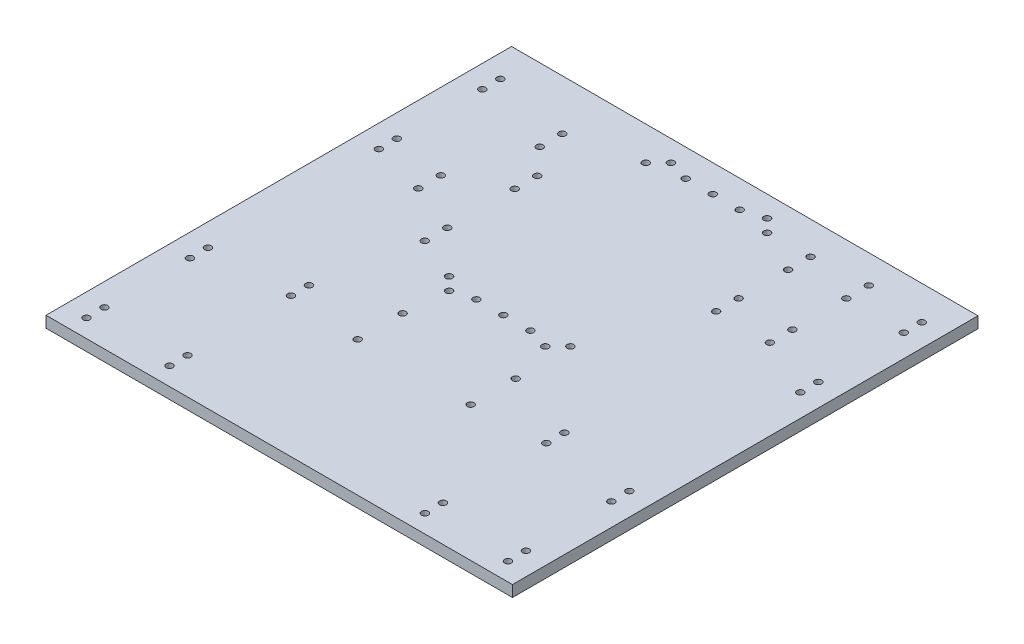
SolidWorks part; units mm, degrees
ref_plane "Front Plane" through (0, 0, 0) normal (0, 0, 1) x (1, 0, 0)
ref_plane "Top Plane" through (0, 0, 0) normal (0, 1, 0) x (1, 0, 0)
ref_plane "Right Plane" through (0, 0, 0) normal (1, 0, 0) x (0, 0, -1)
sketch "Sketch1" plane through (0, 0, 0) normal (0, 1, 0) x (1, 0, 0)
  line L1 (131.7003, -127) -> (-131.7003, -127)
  line L2 (131.7003, -127) -> (131.7003, 127)
  line L3 (131.7003, 127) -> (-131.7003, 127)
  line L4 (-131.7003, -127) -> (-131.7003, 127)
  line L5 (131.7003, -127) -> (-131.7003, 127) construction
  line L6 (131.7003, 127) -> (-131.7003, -127) construction
  point P0 (0, 0)
  dimension "D1" = 263.4005
  dimension "D2" = 254
extrude "Boss-Extrude1" add sketch "Sketch1" along normal blind 6.35
hole_wizard "#6 Clearance Hole1" positions "Sketch3" profile "Sketch4" hole size "#6" standard "ANSI Inch" end condition through all
sketch "Sketch3" plane through (0, 6.35, 0) normal (0, 1, 0) x (1, 0, 0)
  line L0 (131.7003, 127) -> (-131.7003, 127) construction
  line L1 (119.0003, 116.84) -> (119.0003, 106.68)
  line L3 (119.0003, 58.42) -> (119.0003, 48.26)
  line L5 (131.7003, -127) -> (131.7003, 127) construction
  point P0 (119.0003, 116.84)
  point P2 (119.0003, 106.68)
  point P4 (119.0003, 58.42)
  point P6 (119.0003, 48.26)
  dimension "D1" = 10.16
  dimension "D2" = 10.16
  dimension "D3" = 48.26
  dimension "D4" = 12.7
  dimension "D5" = 12.7
  dimension "D6" = 10.16
sketch "Sketch4" plane through (119.0003, 6.35, -116.84) normal (1, 0, 0) x (0, 0, 1)
  line L0 (0, 0) -> (0, 6.35)
  line L1 (0, 6.35) -> (1.8986, 6.35)
  line L2 (1.8986, 6.35) -> (1.8986, 0)
  line L5 (1.8986, 0) -> (0, 0)
  line L11 (0, -6.35) -> (0, 107.95) construction
  dimension "Thru Hole Dia." = 3.7973
  dimension "Thru Hole Depth" = 6.35
ref_plane "Plane1" through (0, 0, 0) normal (0, 0, -1) x (-1, 0, 0)
mirror "Mirror1" about plane through (0, 0, 0) normal (0, 0, -1) of "#6 Clearance Hole1"
hole_wizard "#6 Clearance Hole2" positions "Sketch5" profile "Sketch6" hole size "#6" standard "ANSI Inch" end condition through all
sketch "Sketch5" plane through (0, 6.35, 0) normal (0, 1, 0) x (1, 0, 0)
  line L0 (86.0793, 119.8956) -> (86.0793, 107.1956)
  line L2 (86.0793, 76.7156) -> (86.0793, 64.0156)
  line L4 (131.7003, -127) -> (131.7003, 127) construction
  line L5 (131.7003, 127) -> (-131.7003, 127) construction
  point P0 (86.0793, 119.8956)
  point P2 (86.0793, 107.1956)
  point P4 (86.0793, 76.7156)
  point P6 (86.0793, 64.0156)
  dimension "D1" = 45.6209
  dimension "D2" = 45.6209
  dimension "D3" = 12.7
  dimension "D4" = 12.7
  dimension "D5" = 7.1044
  dimension "D6" = 30.48
sketch "Sketch6" plane through (86.0793, 6.35, -119.8956) normal (1, 0, 0) x (0, 0, 1)
  line L0 (0, 0) -> (0, 6.35)
  line L1 (0, 6.35) -> (1.8986, 6.35)
  line L2 (1.8986, 6.35) -> (1.8986, 0)
  line L5 (1.8986, 0) -> (0, 0)
  line L11 (0, -6.35) -> (0, 107.95) construction
  dimension "Thru Hole Dia." = 3.7973
  dimension "Thru Hole Depth" = 6.35
hole_wizard "#6 Clearance Hole3" positions "Sketch7" profile "Sketch8" hole size "#6" standard "ANSI Inch" end condition through all
sketch "Sketch7" plane through (0, 6.35, 0) normal (0, 1, 0) x (1, 0, 0)
  line L0 (55.5993, 76.802) -> (55.5993, 64.102)
  line L3 (55.5993, 117.442) -> (55.5993, 104.742)
  circle A0 centre (86.0793, 107.1956) radius 1.8986 construction
  circle A1 centre (86.0793, 64.0156) radius 1.8986 construction
  circle A3 centre (86.0793, 119.8956) radius 1.8986 construction
  point P0 (55.5993, 117.442)
  point P2 (55.5993, 104.742)
  point P4 (55.5993, 76.802)
  point P6 (55.5993, 64.102)
  dimension "D6" = 27.94
  dimension "D1" = 12.7
  dimension "D2" = 12.7
  dimension "D3" = 30.48
  dimension "D4" = 30.48
  dimension "D5" = 2.4536
sketch "Sketch8" plane through (55.5993, 6.35, -117.442) normal (1, 0, 0) x (0, 0, 1)
  line L0 (0, 0) -> (0, 6.35)
  line L1 (0, 6.35) -> (1.8986, 6.35)
  line L2 (1.8986, 6.35) -> (1.8986, 0)
  line L5 (1.8986, 0) -> (0, 0)
  line L11 (0, -6.35) -> (0, 107.95) construction
  dimension "Thru Hole Dia." = 3.7973
  dimension "Thru Hole Depth" = 6.35
hole_wizard "#6 Clearance Hole4" positions "Sketch9" profile "Sketch10" hole size "#6" standard "ANSI Inch" end condition through all
sketch "Sketch9" plane through (0, 6.35, 0) normal (0, 1, 0) x (1, 0, 0)
  line L0 (72.1119, -38.1) -> (72.1119, -48.26)
  line L2 (72.1119, -106.68) -> (72.1119, -116.84)
  line L4 (131.7003, -127) -> (131.7003, 127) construction
  line L5 (-131.7003, -127) -> (131.7003, -127) construction
  point P0 (72.1119, -38.1)
  point P2 (72.1119, -48.26)
  point P4 (72.1119, -106.68)
  point P6 (72.1119, -116.84)
  dimension "D1" = 10.16
  dimension "D2" = 10.16
  dimension "D3" = 59.5884
  dimension "D4" = 59.5884
  dimension "D5" = 58.42
  dimension "D6" = 10.16
sketch "Sketch10" plane through (72.1119, 6.35, 38.1) normal (1, 0, 0) x (0, 0, 1)
  line L0 (0, 0) -> (0, 6.35)
  line L1 (0, 6.35) -> (1.8986, 6.35)
  line L2 (1.8986, 6.35) -> (1.8986, 0)
  line L5 (1.8986, 0) -> (0, 0)
  line L11 (0, -6.35) -> (0, 107.95) construction
  dimension "Thru Hole Dia." = 3.7973
  dimension "Thru Hole Depth" = 6.35
ref_plane "Plane2" through (0, 0, 0) normal (-1, 0, 0) x (0, 0, 1)
mirror "Mirror2" about plane through (0, 0, 0) normal (-1, 0, 0) of "#6 Clearance Hole4", "#6 Clearance Hole1", "Mirror1"
hole_wizard "#6 Clearance Hole5" positions "Sketch11" profile "Sketch12" hole size "#6" standard "ANSI Inch" end condition through all
sketch "Sketch11" plane through (0, 6.35, 0) normal (0, 1, 0) x (1, 0, 0)
  line L0 (-74.6519, 107.475) -> (-74.6519, 94.775)
  line L2 (-88.6219, 52.8626) -> (-88.6219, 40.1626)
  line L4 (131.7003, 127) -> (-131.7003, 127) construction
  line L5 (-131.7003, 127) -> (-131.7003, -127) construction
  point P0 (-74.6519, 107.475)
  point P2 (-74.6519, 94.775)
  point P4 (-88.6219, 52.8626)
  point P6 (-88.6219, 40.1626)
  dimension "D1" = 12.7
  dimension "D2" = 12.7
  dimension "D3" = 19.525
  dimension "D4" = 43.0784
  dimension "D5" = 57.0484
  dimension "D6" = 41.9125
sketch "Sketch12" plane through (-74.6519, 6.35, -107.475) normal (1, 0, 0) x (0, 0, 1)
  line L0 (0, 0) -> (0, 6.35)
  line L1 (0, 6.35) -> (1.8986, 6.35)
  line L2 (1.8986, 6.35) -> (1.8986, 0)
  line L5 (1.8986, 0) -> (0, 0)
  line L11 (0, -6.35) -> (0, 107.95) construction
  dimension "Thru Hole Dia." = 3.7973
  dimension "Thru Hole Depth" = 6.35
hole_wizard "#6 Clearance Hole6" positions "Sketch13" profile "Sketch14" hole size "#6" standard "ANSI Inch" end condition through all
sketch "Sketch13" plane through (0, 6.35, 0) normal (0, 1, 0) x (1, 0, 0)
  line L0 (-61.1569, 79.85) -> (-61.1569, 67.15)
  line L2 (-61.1569, 29.05) -> (-61.1569, 16.35)
  line L4 (-131.7003, 127) -> (-131.7003, -127) construction
  line L5 (131.7003, 127) -> (-131.7003, 127) construction
  point P0 (-61.1569, 79.85)
  point P2 (-61.1569, 67.15)
  point P4 (-61.1569, 29.05)
  point P6 (-61.1569, 16.35)
  dimension "D1" = 12.7
  dimension "D2" = 12.7
  dimension "D3" = 70.5434
  dimension "D4" = 70.5434
  dimension "D5" = 110.65
  dimension "D6" = 47.15
sketch "Sketch14" plane through (-61.1569, 6.35, -79.85) normal (1, 0, 0) x (0, 0, 1)
  line L0 (0, 0) -> (0, 6.35)
  line L1 (0, 6.35) -> (1.8986, 6.35)
  line L2 (1.8986, 6.35) -> (1.8986, 0)
  line L5 (1.8986, 0) -> (0, 0)
  line L11 (0, -6.35) -> (0, 107.95) construction
  dimension "Thru Hole Dia." = 3.7973
  dimension "Thru Hole Depth" = 6.35
hole_wizard "#6 Clearance Hole8" positions "Sketch15" profile "Sketch16" hole size "#6" standard "ANSI Inch" end condition through all
sketch "Sketch15" plane through (0, 6.35, 0) normal (0, 1, 0) x (1, 0, 0)
  line L2 (-36.9176, -1.2929) -> (-29.8056, -1.2929)
  line L3 (-36.9176, -1.2929) -> (-36.9176, 5.8191)
  line L4 (-36.9176, 5.8191) -> (-29.8056, 5.8191)
  line L5 (-29.8056, -1.2929) -> (-29.8056, 5.8191)
  line L6 (131.7003, 127) -> (-131.7003, 127) construction
  line L7 (-131.7003, 127) -> (-131.7003, -127) construction
  point P0 (-36.9176, 5.8191)
  point P6 (-29.8056, -1.2929)
  dimension "D1" = 94.7826
  dimension "D2" = 7.112
  dimension "D3" = 7.112
  dimension "D4" = 121.1809
sketch "Sketch16" plane through (-36.9176, 6.35, -5.8191) normal (1, 0, 0) x (0, 0, 1)
  line L0 (0, 0) -> (0, 6.35)
  line L1 (0, 6.35) -> (1.8986, 6.35)
  line L2 (1.8986, 6.35) -> (1.8986, 0)
  line L5 (1.8986, 0) -> (0, 0)
  line L11 (0, -6.35) -> (0, 107.95) construction
  dimension "Thru Hole Dia." = 3.7973
  dimension "Thru Hole Depth" = 6.35
hole_wizard "#6 Clearance Hole9" positions "Sketch17" profile "Sketch18" hole size "#6" standard "ANSI Inch" end condition through all
sketch "Sketch17" plane through (0, 6.35, 0) normal (0, 1, 0) x (1, 0, 0)
  line L1 (-36.9176, 116.8603) -> (-29.8056, 116.8603)
  line L2 (-36.9176, 116.8603) -> (-36.9176, 123.9723)
  line L3 (-36.9176, 123.9723) -> (-29.8056, 123.9723)
  line L4 (-29.8056, 116.8603) -> (-29.8056, 123.9723)
  circle A1 centre (-36.9176, 5.8191) radius 1.8987 construction
  circle A3 centre (-29.8056, -1.2929) radius 1.8986 construction
  point P2 (-29.8056, 123.9723)
  point P4 (-36.9176, 116.8603)
  dimension "D1" = 125.2652
  dimension "D2" = 7.112
  dimension "D3" = 7.112
  dimension "D4" = 0
sketch "Sketch18" plane through (-29.8056, 6.35, -123.9723) normal (1, 0, 0) x (0, 0, 1)
  line L0 (0, 0) -> (0, 6.35)
  line L1 (0, 6.35) -> (1.8986, 6.35)
  line L2 (1.8986, 6.35) -> (1.8986, 0)
  line L5 (1.8986, 0) -> (0, 0)
  line L11 (0, -6.35) -> (0, 107.95) construction
  dimension "Thru Hole Dia." = 3.7973
  dimension "Thru Hole Depth" = 6.35
hole_wizard "#6 Clearance Hole10" positions "Sketch19" profile "Sketch20" hole size "#6" standard "ANSI Inch" end condition through all
sketch "Sketch19" plane through (0, 6.35, 0) normal (0, 1, 0) x (1, 0, 0)
  line L0 (-17.8903, 120.4163) -> (12.5893, 120.4163)
  line L1 (12.5893, 120.4163) -> (-2.6505, 120.4163)
  line L3 (24.5046, 123.9723) -> (31.6166, 123.9723)
  line L4 (24.5046, 123.9723) -> (24.5046, 116.8603)
  line L5 (24.5046, 116.8603) -> (31.6166, 116.8603)
  line L6 (31.6166, 123.9723) -> (31.6166, 116.8603)
  line L9 (24.5046, -1.2929) -> (31.6166, -1.2929)
  line L10 (24.5046, -1.2929) -> (24.5046, 5.8191)
  line L11 (24.5046, 5.8191) -> (31.6166, 5.8191)
  line L12 (31.6166, -1.2929) -> (31.6166, 5.8191)
  circle A0 centre (-29.8056, -1.2929) radius 1.8986 construction
  circle A1 centre (-29.8056, 123.9723) radius 1.8987 construction
  point P0 (-17.8905, 2.2631)
  point P2 (-2.6505, 2.2631)
  point P4 (12.5895, 2.2631)
  point P10 (-17.8903, 120.4163)
  point P12 (-2.6505, 120.4952)
  point P14 (12.5893, 120.4163)
  point P32 (24.5046, 123.9723)
  point P34 (31.6166, 116.8603)
  point P36 (24.5046, -1.2929)
  point P38 (31.6166, 5.8191)
  dimension "D1" = 27.1551
  dimension "D4" = 3.556
  dimension "D5" = 3.556
  dimension "D2" = 15.24
  dimension "D3" = 15.24
  dimension "D6" = 3.556
  dimension "D7" = 15.24
  dimension "D8" = 15.24
  dimension "D9" = 27.1551
  dimension "D10" = 3.556
  dimension "D11" = 27.1551
  dimension "D12" = 7.112
  dimension "D13" = 7.112
  dimension "D14" = 3.556
  dimension "D15" = 7.112
  dimension "D16" = 7.112
  dimension "D17" = 3.556
  dimension "D18" = 11.9151
sketch "Sketch20" plane through (-17.8905, 6.35, -2.2631) normal (1, 0, 0) x (0, 0, 1)
  line L0 (0, 0) -> (0, 6.35)
  line L1 (0, 6.35) -> (1.8986, 6.35)
  line L2 (1.8986, 6.35) -> (1.8986, 0)
  line L5 (1.8986, 0) -> (0, 0)
  line L11 (0, -6.35) -> (0, 107.95) construction
  dimension "Thru Hole Dia." = 3.7973
  dimension "Thru Hole Depth" = 6.35
hole_wizard "#6 Clearance Hole7" positions "Sketch21" profile "Sketch22" hole size "#6" standard "ANSI Inch" end condition through all
sketch "Sketch21" plane through (0, 6.35, 0) normal (0, 1, 0) x (1, 0, 0)
  line L1 (-31.9215, -25.4) -> (31.9214, -25.4)
  line L2 (-31.9215, -25.4) -> (-31.9214, -50.8)
  line L3 (-31.9214, -50.8) -> (31.9214, -50.8)
  line L4 (31.9214, -25.4) -> (31.9214, -50.8)
  line L5 (-131.7003, -127) -> (131.7003, -127) construction
  line L6 (0, 3.4925) -> (0, -3.4925) construction
  point P0 (-31.9215, -25.4)
  point P2 (-31.9214, -50.8)
  point P4 (31.9214, -50.8)
  point P6 (31.9214, -25.4)
  point P94 (0, -25.4)
  dimension "D1" = 63.8429
  dimension "D2" = 25.4
  dimension "D3" = 76.2
  dimension "D4" = 0
sketch "Sketch22" plane through (-31.9215, 6.35, 25.4) normal (1, 0, 0) x (0, 0, 1)
  line L0 (0, 0) -> (0, 6.35)
  line L1 (0, 6.35) -> (1.8986, 6.35)
  line L2 (1.8986, 6.35) -> (1.8986, 0)
  line L5 (1.8986, 0) -> (0, 0)
  line L11 (0, -6.35) -> (0, 107.95) construction
  dimension "Thru Hole Dia." = 3.7973
  dimension "Thru Hole Depth" = 6.35
sketch "Sketch23" plane through (0, 6.35, 0) normal (0, 1, 0) x (1, 0, 0)
  line L0 (131.7003, 127) -> (-131.7003, 127) construction
  line L1 (-131.7003, 127) -> (131.7003, 127)
  line L2 (-131.7003, 127) -> (-131.7003, 135.89)
  line L3 (-131.7003, 135.89) -> (131.7003, 135.89)
  line L4 (131.7003, 127) -> (131.7003, 135.89)
  line L5 (-131.7003, 127) -> (-131.7003, -127) construction
  dimension "D1" = 8.89
extrude "Boss-Extrude2" add sketch "Sketch23" against normal blind 6.35
sketch "Sketch24" plane through (0, 6.35, 0) normal (0, 1, 0) x (1, 0, 0)
  circle A0 centre (-29.8056, 123.9723) radius 1.8987
  circle A1 centre (24.5046, 123.9723) radius 1.8987
  dimension "D1" = 3.7973
  dimension "D2" = 3.7973
